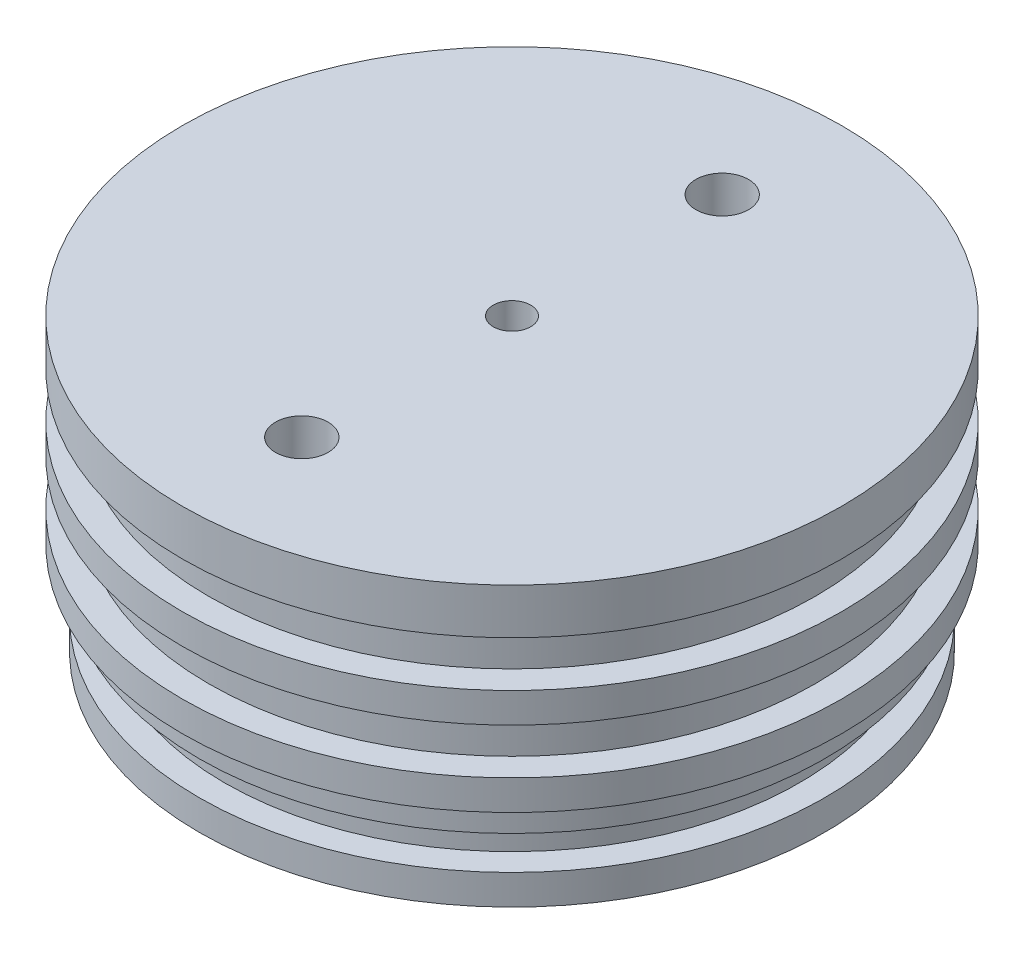
SolidWorks part; units mm, degrees
ref_plane "Front Plane" through (0, 0, 0) normal (0, 0, 1) x (1, 0, 0)
ref_plane "Top Plane" through (0, 0, 0) normal (0, 1, 0) x (1, 0, 0)
ref_plane "Right Plane" through (0, 0, 0) normal (1, 0, 0) x (0, 0, -1)
sketch "Sketch1" plane through (0, 0, 0) normal (0, 1, 0) x (1, 0, 0)
  circle A0 centre (0, 0) radius 69.723
  dimension "D1" = 139.446
extrude "Boss-Extrude1" add sketch "Sketch1" along normal blind 41.656
ref_plane "Plane1" through (69.723, 0, 0) normal (1, 0, 0) x (0, 0, -1)
sketch "Sketch3" plane through (0, 0, 0) normal (1, 0, 0) x (0, 0, -1)
  line L0 (69.723, 0) -> (69.723, 41.656) construction
  line L1 (69.723, 32.004) -> (64.135, 32.004)
  line L2 (69.723, 32.004) -> (69.723, 22.352)
  line L3 (69.723, 22.352) -> (64.135, 22.352)
  line L4 (64.135, 32.004) -> (64.135, 22.352)
  line L5 (-69.723, 0) -> (69.723, 0) construction
  line L6 (69.723, 16.002) -> (64.135, 16.002)
  line L7 (69.723, 16.002) -> (69.723, 6.35)
  line L8 (69.723, 6.35) -> (64.135, 6.35)
  line L9 (64.135, 16.002) -> (64.135, 6.35)
  dimension "D1" = 9.652
  dimension "D2" = 9.652
  dimension "D3" = 64.135
  dimension "D4" = 64.135
  dimension "D5" = 6.35
  dimension "D6" = 6.35
ref_axis "Axis1" through (0, 41.656, 0) along (0, -1, 0)
revolve "Cut-Revolve1" cut sketch "Sketch3" angle 360 about axis through (0, 41.656, 0) along (0, -1, 0)
sketch "Sketch4" plane through (0, 0, 0) normal (0, -1, 0) x (1, 0, 0)
  circle A0 centre (0, 0) radius 66.167
  dimension "D1" = 132.334
extrude "Boss-Extrude2" add sketch "Sketch4" along normal blind 19.8374
sketch "Sketch5" plane through (0, 0, 0) normal (1, 0, 0) x (0, 0, -1)
  line L0 (66.167, -19.8374) -> (66.167, 0) construction
  line L1 (66.167, -13.4874) -> (60.7695, -13.4874)
  line L2 (66.167, -13.4874) -> (66.167, -6.35)
  line L3 (66.167, -6.35) -> (60.7695, -6.35)
  line L4 (60.7695, -13.4874) -> (60.7695, -6.35)
  line L6 (-66.167, -19.8374) -> (66.167, -19.8374) construction
  dimension "D1" = 60.7695
  dimension "D2" = 7.1374
  dimension "D3" = 6.35
revolve "Cut-Revolve2" cut sketch "Sketch5" angle 360 about axis through (0, 41.656, 0) along (0, -1, 0)
sketch "Sketch7" plane through (0, -19.8374, 0) normal (0, -1, 0) x (1, 0, 0)
  circle A0 centre (0, 0) radius 24.765
  dimension "D1" = 49.53
extrude "Cut-Extrude1" cut sketch "Sketch7" against normal blind 38.1 contours A0
sketch "Sketch8" plane through (0, 41.656, 0) normal (0, 1, 0) x (1, 0, 0)
  line L0 (0, 0) -> (0, 44.45) construction
  line L1 (0, -55) -> (0, 55) construction
  dimension "D1" = 44.45
hole_wizard "Pipe Tap Drill for 1/4 Tap1" positions "3DSketch1" profile "Sketch9" hole size "1/4" standard "ANSI Inch" end condition up to next
sketch3d "3DSketch1"
  point P0 (0, 41.656, -44.45)
sketch "Sketch9" plane through (0, 41.656, -44.45) normal (1, 0, 0) x (0, 0, 1)
  line L0 (0, 0) -> (0, 61.4934)
  line L1 (0, 61.4934) -> (5.5626, 61.4934)
  line L2 (5.5626, 61.4934) -> (5.5626, 0)
  line L5 (5.5626, 0) -> (0, 0)
  line L11 (0, -6.35) -> (0, 107.95) construction
  dimension "Thru Hole Dia." = 11.1252
  dimension "Thru Hole Depth" = 61.4934
mirror "Mirror1" about plane through (0, 0, 0) normal (0, 0, 1) of "Pipe Tap Drill for 1/4 Tap1"
sketch "Sketch13" plane through (0, 41.656, 0) normal (0, 1, 0) x (1, 0, 0)
  point P0 (0, 0)
hole_wizard "Tap Drill for 3/8-16 Tap1" positions "3DSketch4" profile "Sketch16" hole size "3/8-16" standard "ANSI Inch"
sketch3d "3DSketch4"
  point P0 (0, 41.656, 0)
sketch "Sketch16" plane through (0, 41.656, 0) normal (1, 0, 0) x (0, 0, 1)
  line L0 (0, 0) -> (0, 15.0847)
  line L1 (0, 15.0847) -> (3.9687, 12.7)
  line L2 (3.9687, 12.7) -> (3.9687, 0)
  line L5 (3.9687, 0) -> (0, 0)
  line L10 (0, 15.0847) -> (-3.9688, 12.7) construction
  line L11 (0, -6.35) -> (0, 107.95) construction
  dimension "Hole Dia." = 7.9375
  dimension "Hole Depth" = 12.7
  dimension "Drill Angle" = 118
sketch "Sketch21" plane through (0, 41.656, 0) normal (0, 1, 0) x (1, 0, 0)
  point P0 (0, 44.45)
  point P1 (0, -44.45)
hole_wizard "Pipe Tap Drill for 1/4 Tap2" positions "3DSketch9" profile "Sketch23" hole size "1/4" standard "ANSI Inch" end condition up to next
sketch3d "3DSketch9"
  point P0 (0, 41.656, 44.45)
  point P3 (0, 41.656, -44.45)
sketch "Sketch23" plane through (0, 41.656, 44.45) normal (1, 0, 0) x (0, 0, 1)
  line L0 (0, 0) -> (0, 61.4934)
  line L1 (0, 61.4934) -> (5.5626, 61.4934)
  line L2 (5.5626, 61.4934) -> (5.5626, 0)
  line L5 (5.5626, 0) -> (0, 0)
  line L11 (0, -6.35) -> (0, 107.95) construction
  dimension "Thru Hole Dia." = 11.1252
  dimension "Thru Hole Depth" = 61.4934
sketch "snap ring groove" plane through (0, 0, 0) normal (0, 0, 1) x (1, 0, 0)
  line L2 (-66.167, -19.8374) -> (66.167, -19.8374) construction
  line L3 (-24.765, -16.6624) -> (-26.9494, -16.6624)
  line L4 (-24.765, -16.6624) -> (-24.765, -14.8844)
  line L5 (-24.765, -14.8844) -> (-26.9494, -14.8844)
  line L6 (-26.9494, -16.6624) -> (-26.9494, -14.8844)
  line L7 (-24.765, 18.2626) -> (-24.765, -19.8374) construction
  point P9 (-26.9494, -15.7734)
  dimension "D1" = 1.778
  dimension "D2" = 26.9494
  dimension "D3" = 3.175
revolve "Cut-Revolve3" cut sketch "snap ring groove" angle 360 about axis through (0, 41.656, 0) along (0, -1, 0)
